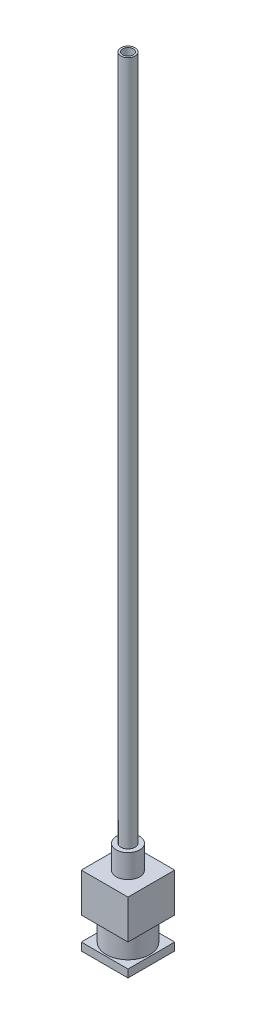
SolidWorks part; units mm, degrees
ref_plane "Front Plane" through (0, 0, 0) normal (0, 0, 1) x (1, 0, 0)
ref_plane "Top Plane" through (0, 0, 0) normal (0, 1, 0) x (1, 0, 0)
ref_plane "Right Plane" through (0, 0, 0) normal (1, 0, 0) x (0, 0, -1)
sketch "Sketch1" plane through (0, 0, 0) normal (0, 1, 0) x (1, 0, 0)
  line L1 (3, -3) -> (-3, -3)
  line L2 (3, -3) -> (3, 3)
  line L3 (3, 3) -> (-3, 3)
  line L4 (-3, -3) -> (-3, 3)
  line L5 (0, 3) -> (0, -3) construction
  line L6 (3, 0) -> (-3, 0) construction
  point P0 (0, 0)
  dimension "D1" = 6
  dimension "D2" = 6
extrude "Boss-Extrude1" add sketch "Sketch1" along normal blind 9
sketch "Sketch2" plane through (0, 9, 0) normal (0, 1, 0) x (1, 0, 0)
  circle A0 centre (0, 0) radius 1.5
  dimension "D1" = 3
extrude "Boss-Extrude2" add sketch "Sketch2" along normal blind 3
sketch "Sketch3" plane through (0, 12, 0) normal (0, 1, 0) x (1, 0, 0)
  circle A0 centre (0, 0) radius 0.68
  circle A1 centre (0, 0) radius 0.92
  dimension "D1" = 1.36
  dimension "D2" = 1.84
extrude "Cut-Extrude1" cut sketch "Sketch3" against normal through all both and the other way through all contours A0
extrude "Boss-Extrude3" add sketch "Sketch3<3>" along normal blind 88
sketch "Sketch3<3>" plane through (0, 12, 0) normal (0, 1, 0) x (1, 0, 0) same geometry as "Sketch3"
sketch "Sketch4" plane through (0, 0, 0) normal (0, -1, 0) x (1, 0, 0)
  circle A1 centre (0, 0) radius 2
  dimension "D1" = 4
extrude "Cut-Extrude2" cut sketch "Sketch4" against normal blind 8
sketch "Sketch6" plane through (0, 0, 0) normal (0, -1, 0) x (1, 0, 0)
  line L4 (-3, 3) -> (-3, -3)
  line L5 (-3, -3) -> (3, -3)
  line L6 (3, -3) -> (3, 3)
  line L7 (3, 3) -> (-3, 3)
  line L8 (-3, 3) -> (-3, -3)
  line L9 (-3, -3) -> (3, -3)
  line L10 (3, -3) -> (3, 3)
  line L11 (3, 3) -> (-3, 3)
  circle A0 centre (0, 0) radius 2.8
  dimension "D1" = 5.6
  dimension "D2" = 0
extrude "Cut-Extrude3" cut sketch "Sketch6" against normal offset from surface (3 mm away) 4 from offset 1 up to face at (0, 0, -2) offset against normal yes
